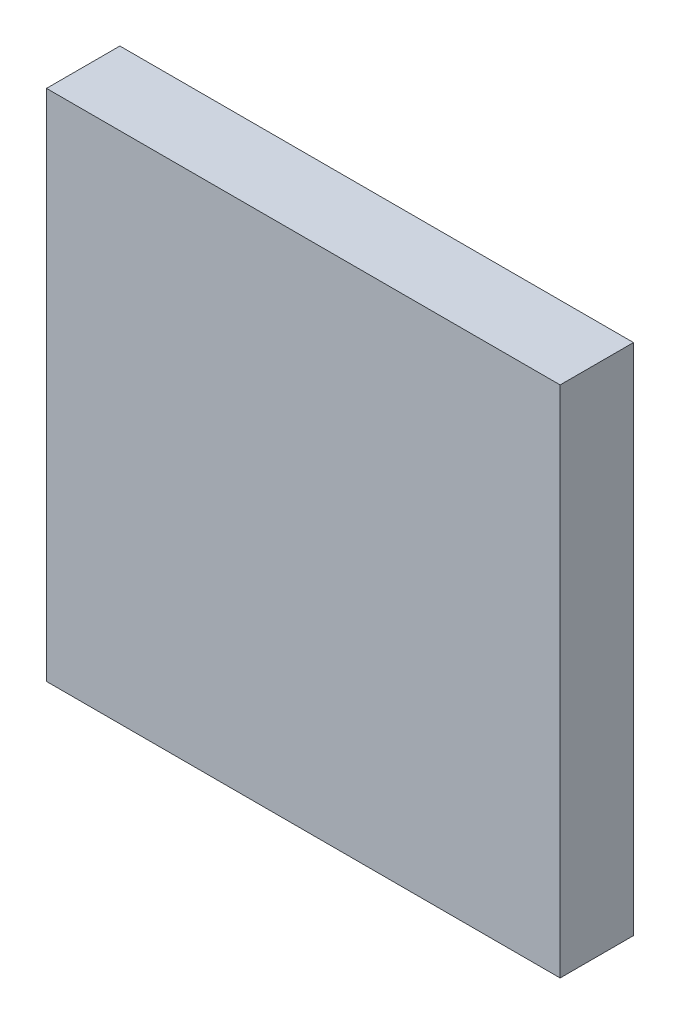
SolidWorks part; units mm, degrees
material "Silicon Dioxide"
ref_plane "Front Plane" through (0, 0, 0) normal (0, 0, 1) x (1, 0, 0)
ref_plane "Top Plane" through (0, 0, 0) normal (0, 1, 0) x (1, 0, 0)
ref_plane "Right Plane" through (0, 0, 0) normal (1, 0, 0) x (0, 0, -1)
sketch "Sketch1" plane through (0, 0, 0) normal (0, 0, 1) x (1, 0, 0)
  line L1 (-17.5, 17.5) -> (17.5, 17.5)
  line L2 (-17.5, 17.5) -> (-17.5, -17.5)
  line L3 (-17.5, -17.5) -> (17.5, -17.5)
  line L4 (17.5, 17.5) -> (17.5, -17.5)
  line L5 (-17.5, 17.5) -> (17.5, -17.5) construction
  line L6 (-17.5, -17.5) -> (17.5, 17.5) construction
  point P0 (0, 0)
  dimension "D1" = 35
  dimension "D2" = 35
extrude "Mirror" add sketch "Sketch1" along normal blind 5
